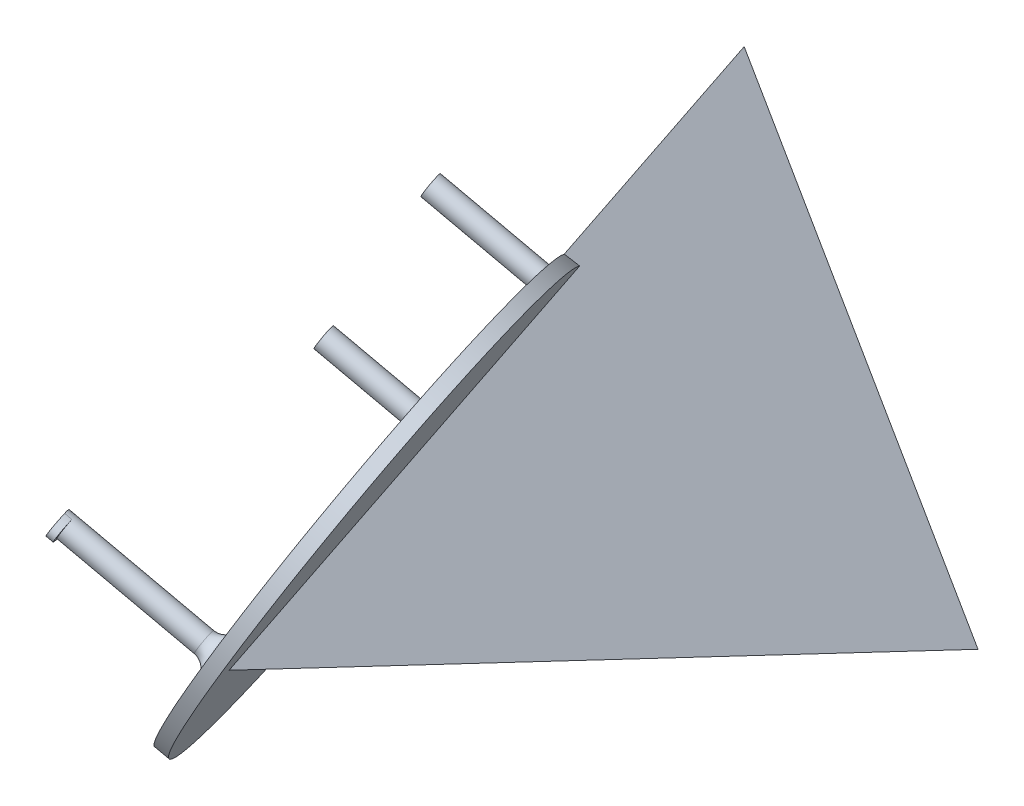
SolidWorks part; units mm, degrees
ref_plane "Ebene vorne" through (0, 0, 0) normal (0, 0, 1) x (1, 0, 0)
ref_plane "Ebene oben" through (0, 0, 0) normal (0, 1, 0) x (1, 0, 0)
ref_plane "Ebene rechts" through (0, 0, 0) normal (1, 0, 0) x (0, 0, -1)
sketch "Skizze1" plane through (0, 0, 0) normal (0, 0, 1) x (1, 0, 0)
  line L0 (0, 30.3109) -> (-17.5, 0)
  line L1 (-17.5, 0) -> (17.5, 0)
  line L2 (17.5, 0) -> (0, 30.3109)
  dimension "D1" = 35
  dimension "D2" = 35
  dimension "D3" = 35
  dimension "D4" = 0
extrude "Aufsatz-Linear austragen1" add sketch "Skizze1" along normal blind 40
chamfer "Fase1" distance 40 angle 14 3 edges at (0, 0, 40) (8.75, 15.1554, 40) (-8.75, 15.1554, 40) first distance on face at (0, 0, 20) first distance on face at (8.75, 15.1554, 20) first distance on face at (-8.75, 15.1554, 20)
shell "Wandung1" thickness 2 removed face at (0, 10.1036, 0)
sketch "Skizze2" plane through (-12.3568, 7.1342, 3.5575) normal (-0.8403, 0.4851, 0.2419) x (0.2095, -0.121, 0.9703)
  line L0 (37.5581, 8.976) -> (37.5581, 8.524) construction
  circle A0 centre (22.5581, 8.75) radius 17
  point P4 (37.5581, 8.75)
  dimension "D1" = 34
  dimension "D2" = 15
extrude "Aufsatz-Linear austragen2" add sketch "Skizze2" against normal blind 1
sketch "Skizze3" plane through (-12.3568, 7.1342, 3.5575) normal (-0.8403, 0.4851, 0.2419) x (0.2095, -0.121, 0.9703)
  circle A0 centre (36.5581, 8.75) radius 0.8
  arc A1 (10.2108, -2.9352) -> (10.2108, 20.4352) centre (22.5581, 8.75) ccw construction
  dimension "D1" = 14
  dimension "D2" = 1.6
extrude "Aufsatz-Linear austragen3" add sketch "Skizze3" along normal blind 11
fillet "Verrundung1" radius 1 1 edges at (-0.7225, 9.597, 39.0297)
sketch "Skizze4" plane through (-12.3568, 7.1342, 3.5575) normal (-0.8403, 0.4851, 0.2419) x (0.2095, -0.121, 0.9703)
  circle A0 centre (9.5581, 16.75) radius 0.8
  circle A1 centre (9.5581, 0.75) radius 0.8
  circle A2 centre (36.5581, 8.75) radius 0.8 construction
  arc A3 (10.2108, -2.9352) -> (10.2108, 20.4352) centre (22.5581, 8.75) ccw construction
  dimension "D1" = 8
  dimension "D2" = 8
  dimension "D3" = 13
  dimension "D4" = 1.6
  dimension "D5" = 13
  dimension "D6" = 1.6
extrude "Aufsatz-Linear austragen4" add sketch "Skizze4" along normal blind 8
sketch "Skizze5" plane through (-21.6002, 12.4709, 6.2187) normal (-0.8403, 0.4851, 0.2419) x (0.2095, -0.121, 0.9703)
  arc A0 (36.5581, 9.55) -> (36.5581, 7.95) centre (36.5581, 8.75) ccw
  ellipse E0 centre (36.5581, 8.75) end of major axis (37.7581, 8.75) minor radius 0.8 (36.5581, 7.95) -> (36.5581, 9.55) ccw
  dimension "D1" = 1.2
extrude "Aufsatz-Linear austragen5" add sketch "Skizze5" against normal blind 0.5
sketch "Skizze6" plane through (0, 0, 0) normal (0, -0.9703, 0.2419) x (1, 0, 0)
  line L0 (-14.4935, 2) -> (14.4935, 2)
  line L1 (14.4935, 2) -> (0, 36.5889)
  line L2 (0, 36.5889) -> (-14.4935, 2)
  line L3 (17.5, 0) -> (0.595, 40.344) construction
  line L4 (-17.5, 0) -> (17.5, 0) construction
  line L5 (0.595, 40.344) -> (-10.7361, 13.3022) construction
  line L6 (-11.6852, 13.8772) -> (-17.5, 0) construction
  dimension "D1" = 2
  dimension "D2" = 2
  dimension "D3" = 2
